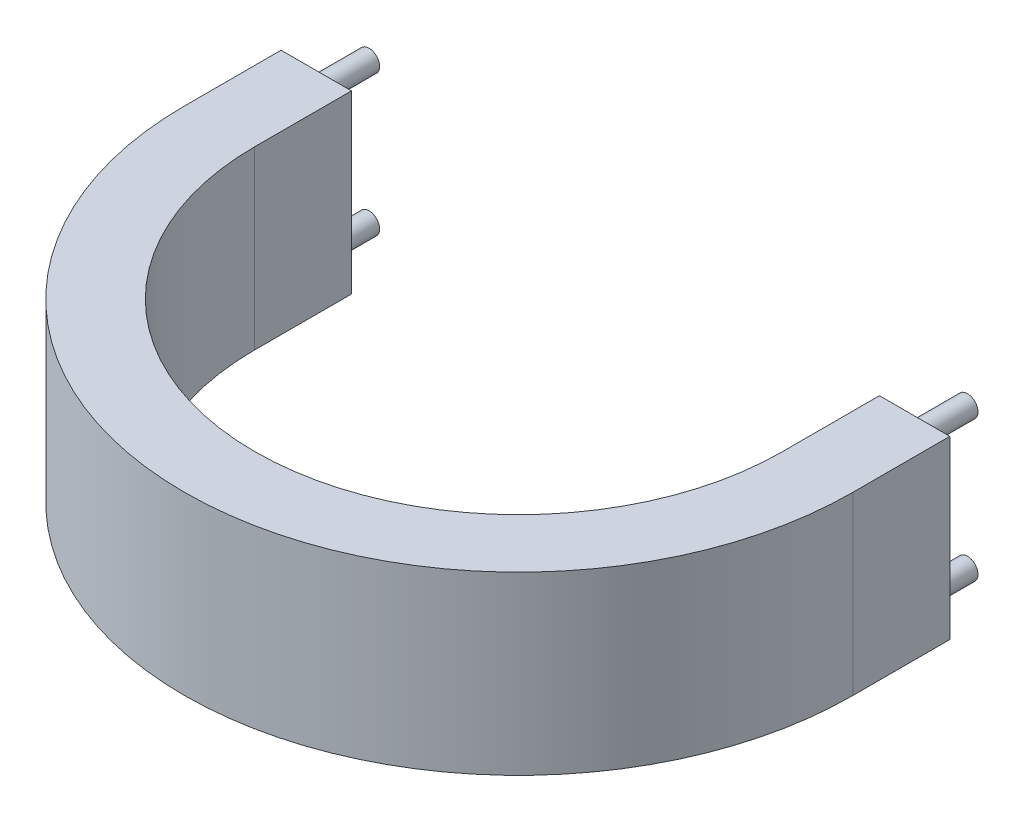
SolidWorks part; units mm, degrees
ref_plane "Front" through (0, 0, 0) normal (0, 0, 1) x (1, 0, 0)
ref_plane "Top" through (0, 0, 0) normal (0, 1, 0) x (1, 0, 0)
ref_plane "Right" through (0, 0, 0) normal (1, 0, 0) x (0, 0, -1)
sketch "草图2" plane through (0, 0, 0) normal (0, 1, 0) x (1, 0, 0)
  line L0 (-30, 0) -> (-30, 11)
  line L2 (-38, 0) -> (-38, 11)
  line L3 (-38, 11) -> (-30, 11)
  line L4 (38, 0) -> (38, 11)
  line L5 (30, 0) -> (30, 11)
  line L6 (30, 11) -> (38, 11)
  arc A0 (-38, 0) -> (38, 0) centre (0, 0) ccw
  arc A1 (-30, 0) -> (30, 0) centre (0, 0) ccw
  dimension "D1" = 11
extrude "凸台-拉伸1" add sketch "草图2" along normal blind 20
sketch "草图3" plane through (0, 0, -11) normal (0, 0, -1) x (-1, 0, 0)
  line L0 (-34, 20) -> (-34, 0) construction
  line L1 (-38, 20) -> (-30, 20) construction
  line L2 (-38, 0) -> (-30, 0) construction
  line L3 (34, 20) -> (34, 0) construction
  line L4 (30, 20) -> (38, 20) construction
  line L5 (30, 0) -> (38, 0) construction
  line L6 (-38, 10) -> (38, 10) construction
  line L7 (-38, 20) -> (-38, 0) construction
  line L8 (38, 20) -> (38, 0) construction
  circle A0 centre (-34, 18) radius 1.2
  circle A1 centre (-34, 2) radius 1.2
  circle A2 centre (34, 18) radius 1.2
  circle A3 centre (34, 2) radius 1.2
extrude "凸台-拉伸2" add sketch "草图3" along normal blind 6
